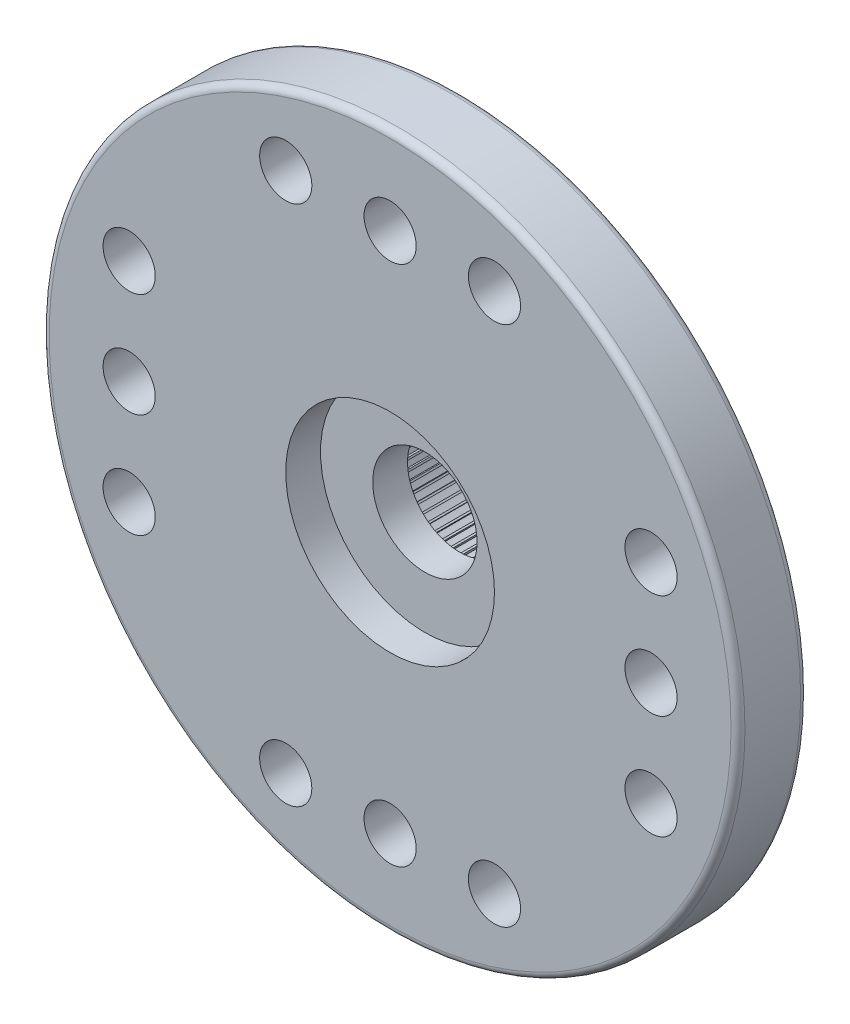
SolidWorks part; units mm, degrees
ref_plane "Ön Düzlem" through (0, 0, 0) normal (0, 0, 1) x (1, 0, 0)
ref_plane "Üst Düzlem" through (0, 0, 0) normal (0, 1, 0) x (1, 0, 0)
ref_plane "Sağ Düzlem" through (0, 0, 0) normal (1, 0, 0) x (0, 0, -1)
sketch "Sketch1" plane through (0, 0, 0) normal (0, 0, 1) x (1, 0, 0)
  line L0 (-4, 14.1652) -> (-4, 9.1652) construction
  line L1 (4, 14.1652) -> (4, 9.1652) construction
  line L2 (0, 0) -> (0, 16.75) construction
  line L3 (-4, 9.1652) -> (4, 9.1652) construction
  line L4 (-1.6906, 17.8186) -> (-4, 14.1652) construction
  line L5 (1.6906, 17.8186) -> (4, 14.1652) construction
  circle A0 centre (0, 0) radius 10
  circle A1 centre (0, 0) radius 18.75 construction
  circle A2 centre (0, 16.75) radius 2 construction
  circle A3 centre (0, 0) radius 1.5
  dimension "D1" = 37.5
  dimension "D2" = 20
  dimension "D3" = 4
  dimension "D5" = 3
  dimension "D4" = 5
  dimension "D6" = 8
extrude "Boss-Extrude1" add sketch "Sketch1" along normal blind 2 contours A0 A3 | A2 L4 L0 A0 L1 L5 | A2
sketch "Sketch2" plane through (0, 0, 2) normal (0, 0, 1) x (1, 0, 0)
  line L0 (0, 0) -> (0, 10) construction
  line L1 (0, 7.5) -> (3, 7.5) construction
  line L2 (0, 0) -> (10, 0) construction
  line L3 (7.5, 0) -> (7.5, -3) construction
  line L4 (0, 0) -> (0, -10) construction
  line L5 (0, -7.5) -> (-3, -7.5) construction
  line L6 (0, 0) -> (-10, 0) construction
  line L7 (-7.5, 0) -> (-7.5, 3) construction
  circle A1 centre (0, 7.5) radius 0.75
  circle A2 centre (0, 0) radius 1.5 construction
  circle A3 centre (7.5, 0) radius 0.75
  circle A4 centre (7.5, -3) radius 0.75
  circle A5 centre (0, 0) radius 10 construction
  circle A6 centre (7.5, 3) radius 0.75
  circle A7 centre (3, 7.5) radius 0.75
  circle A8 centre (-3, 7.5) radius 0.75
  circle A9 centre (0, -7.5) radius 0.75
  circle A10 centre (-3, -7.5) radius 0.75
  circle A11 centre (3, -7.5) radius 0.75
  circle A12 centre (-7.5, 0) radius 0.75
  circle A13 centre (-7.5, 3) radius 0.75
  circle A14 centre (-7.5, -3) radius 0.75
  point P18 (0, 0)
  point P23 (0, 0)
  point P31 (0, 0)
  point P39 (0, 0)
  point P41 (0, 0)
  dimension "D1" = 1.5
  dimension "D2" = 7.5
  dimension "D4" = 1.5
  dimension "D5" = 3
  dimension "D3" = 4
extrude "Cut-Extrude1" cut sketch "Sketch2" against normal through all
sketch "Sketch3" plane through (0, 0, 2) normal (0, 0, 1) x (1, 0, 0)
  circle A0 centre (0, 0) radius 3
  dimension "D1" = 6
extrude "Cut-Extrude2" cut sketch "Sketch3" against normal blind 1
sketch "Sketch4" plane through (0, 0, 0) normal (0, 0, -1) x (-1, 0, 0)
  circle A0 centre (0, 0) radius 4
  circle A1 centre (0, 0) radius 3
  dimension "D1" = 8
  dimension "D2" = 6
extrude "Boss-Extrude2" add sketch "Sketch4" along normal blind 4
sketch "Sketch5" plane through (0, 0, -4) normal (0, 0, -1) x (-1, 0, 0)
  line L0 (0, 0) -> (0, -4) construction
  line L2 (0.025, -2.8941) -> (-0.025, -2.8941)
  line L3 (0.025, -2.8941) -> (0.025, -3.3941)
  line L4 (0.025, -3.3941) -> (-0.025, -3.3941)
  line L5 (-0.025, -2.8941) -> (-0.025, -3.3941)
  line L6 (0.025, -2.8941) -> (-0.025, -3.3941) construction
  line L7 (0.025, -3.3941) -> (-0.025, -2.8941) construction
  circle A1 centre (0, 0) radius 4 construction
  point P0 (0, -3.1441)
  dimension "D1" = 0.05
  dimension "D2" = 0.5
extrude "Boss-Extrude3" add sketch "Sketch5" against normal up to surface (4 mm away) up to face at (-3, 0, 0)
pattern_circular "CirPattern3" count 80 over 360 about axis through (0, 0, 0) along (0, 0, 1) of "Boss-Extrude3"
fillet "Fillet3" radius 0.2 4 edges at (10, 0, 0) (10, 0, 2) (4, 0, 0) (-4, 0, -4)
